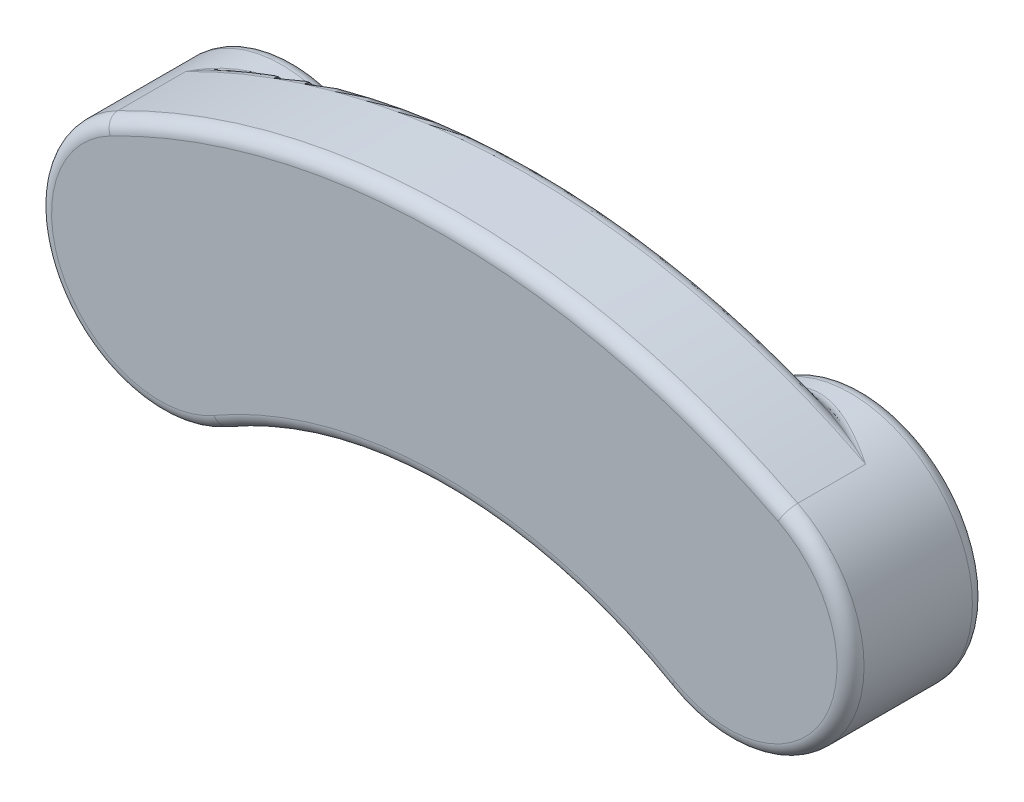
SolidWorks part; units mm, degrees
ref_plane "Front Plane" through (0, 0, 0) normal (0, 0, 1) x (1, 0, 0)
ref_plane "Top Plane" through (0, 0, 0) normal (0, 1, 0) x (1, 0, 0)
ref_plane "Right Plane" through (0, 0, 0) normal (1, 0, 0) x (0, 0, -1)
sketch "Sketch1" plane through (0, 0, 0) normal (0, 0, 1) x (1, 0, 0)
  line L0 (30, 0) -> (-30, 0)
  circle A0 centre (-21, 0) radius 9
  circle A2 centre (21, 0) radius 9
  point P6 (0, 0)
  point P9 (0, 0)
  dimension "D1" = 18
  dimension "D2" = 60
extrude "Boss-Extrude1" add sketch "Sketch1" against normal blind 10 contours L0 A0 | L0 A0 | L0 A2 | L0 A2 region at (-21, -3.8197, 0) region at (21, 3.8197, 0) region at (21, -3.8197, 0) region at (-21, 3.8197, 0)
sketch "Sketch2" plane through (0, 0, 0) normal (0, 0, 1) x (1, 0, 0)
  arc A0 (-25.1087, 8.0074) -> (25.1087, 8.0074) centre (0, -40.9268) cw
  circle A1 centre (-21, 0) radius 9 construction
  circle A2 centre (21, 0) radius 9 construction
  arc A3 (-16.5, -7.7942) -> (16.5, -7.7942) centre (0, -36.3731) cw
  arc A4 (-25.1087, 8.0074) -> (-16.5, -7.7942) centre (-21, 0) cw
  arc A5 (16.5, -7.7942) -> (25.1087, 8.0074) centre (21, 0) cw
  dimension "D1" = 55
  dimension "D2" = 33
extrude "Boss-Extrude2" add sketch "Sketch2" against normal blind 7 contours A5 A0 A4 A3
sketch "Sketch3" plane through (0, 0, -10) normal (0, 0, -1) x (-1, 0, 0)
  line L0 (-17.8606, 0.62) -> (-24.1394, 0.62)
  line L1 (-17.8606, -0.62) -> (-24.1394, -0.62)
  line L2 (-21, 9) -> (-21, -9) construction
  line L3 (24.1394, 0.62) -> (17.8606, 0.62)
  line L4 (24.1394, -0.62) -> (17.8606, -0.62)
  line L5 (21, -9) -> (21, 9) construction
  arc A0 (-24.1394, -0.62) -> (-17.8606, -0.62) centre (-21, 0) ccw
  arc A1 (-17.8606, 0.62) -> (-24.1394, 0.62) centre (-21, 0) ccw
  arc A2 (-16.5, -7.7942) -> (-25.1087, 8.0074) centre (-21, 0) ccw construction
  circle A3 centre (-21, 0) radius 9 construction
  arc A4 (17.8606, -0.62) -> (24.1394, -0.62) centre (21, 0) ccw
  arc A5 (24.1394, 0.62) -> (17.8606, 0.62) centre (21, 0) ccw
  circle A6 centre (21, 0) radius 9 construction
  arc A7 (25.1087, 8.0074) -> (16.5, -7.7942) centre (21, 0) ccw construction
  point P3 (-21, 0.62)
  point P6 (-21, -0.62)
  point P15 (-21, 0)
  point P19 (21, 0.62)
  point P22 (21, -0.62)
  point P31 (21, 0)
  dimension "D1" = 6.4
  dimension "D5" = 6.4
  dimension "D2" = 0.62
  dimension "D3" = 0.62
  dimension "D4" = 0
  dimension "D6" = 0.62
  dimension "D7" = 0.62
  dimension "D8" = 0
extrude "Cut-Extrude1" cut sketch "Sketch3" against normal blind 7
fillet "Fillet1" radius 1 10 edges at (0, -3.3731, 0) (28.9032, -4.3057, 0) (-12, 0, -10) (-28.9032, -4.3057, 0) (-13.0968, 4.3057, -7) (30, 0, -10) (13.0968, 4.3057, -7) (0, -3.3731, -7) (0, 14.0732, -7) (0, 14.0732, 0)
